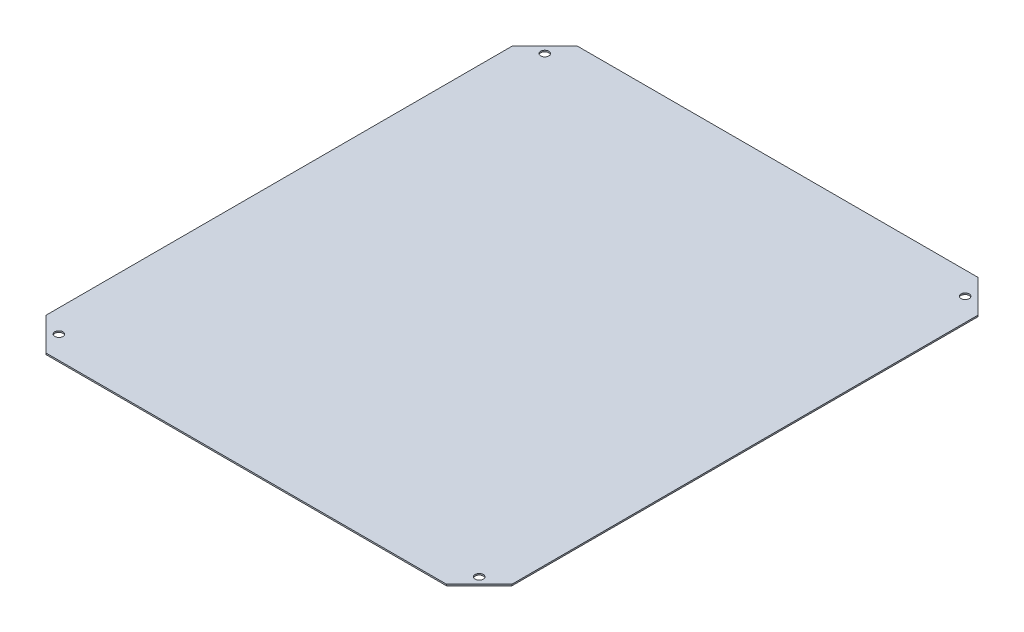
SolidWorks part; units mm, degrees
ref_plane "Front Plane" through (0, 0, 0) normal (0, 0, 1) x (1, 0, 0)
ref_plane "Top Plane" through (0, 0, 0) normal (0, 1, 0) x (1, 0, 0)
ref_plane "Right Plane" through (0, 0, 0) normal (1, 0, 0) x (0, 0, -1)
sketch "Sketch3" plane through (0, 0, 0) normal (0, 1, 0) x (1, 0, 0)
  line L4 (-57.0395, 93.017) -> (57.0395, 93.017)
  line L5 (57.0395, 93.017) -> (110.0725, 146.05)
  line L14 (110.0725, 146.05) -> (128.033, 128.0895)
  line L15 (128.033, 128.0895) -> (75, 75.0565)
  line L16 (75, 75.0565) -> (75, 0)
  line L17 (0, 0) -> (0, 93.017) construction
  line L18 (0, 0) -> (75, 0) construction
  line L19 (-75, 75.0565) -> (-75, -75.0565)
  line L20 (-128.033, 128.0895) -> (-75, 75.0565)
  line L21 (-110.0725, 146.05) -> (-128.033, 128.0895)
  line L22 (-57.0395, 93.017) -> (-110.0725, 146.05)
  line L23 (-57.0395, -93.017) -> (-110.0725, -146.05)
  line L24 (-110.0725, -146.05) -> (-128.033, -128.0895)
  line L25 (-128.033, -128.0895) -> (-75, -75.0565)
  line L26 (75, -75.0565) -> (75, 0)
  line L27 (128.033, -128.0895) -> (75, -75.0565)
  line L28 (110.0725, -146.05) -> (128.033, -128.0895)
  line L29 (57.0395, -93.017) -> (110.0725, -146.05)
  line L30 (-57.0395, -93.017) -> (57.0395, -93.017)
  point P5 (75, 37.5282)
  point P18 (-75, 0)
  dimension "D1" = 25.4
  dimension "D2" = 75
  dimension "D4" = 75
  dimension "D5" = 135
  dimension "D3" = 292.1
extrude "Sheet" add sketch "Sketch3" along normal blind 0.7937
fillet "Fillet1" radius 50 8 edges at (-75, 0.3969, 75.0565) (-57.0395, 0.3969, 93.017) (75, 0.3969, 75.0565) (57.0395, 0.3969, 93.017) (57.0395, 0.3969, -93.017) (75, 0.3969, -75.0565) (-75, 0.3969, -75.0565) (-57.0395, 0.3969, -93.017)
hole_wizard "M4 Clearance Hole1" positions "Sketch4" profile "Sketch5" hole size "M4" standard "ANSI Metric" end condition through all
sketch "Sketch4" plane through (0, 0.7937, 0) normal (0, 1, 0) x (1, 0, 0)
  line L0 (119.0528, 137.0697) -> (55.6644, 73.6814) construction
  line L1 (128.033, 128.0895) -> (110.0725, 146.05) construction
  line L2 (36.3288, 93.017) -> (75, 54.3458) construction
  point P0 (115.5172, 133.5342)
  point P15 (55.6644, 73.6814)
  dimension "D1" = 5
sketch "Sketch5" plane through (115.5172, 0.7937, -133.5342) normal (1, 0, 0) x (0, 0, 1)
  line L0 (0, 0) -> (0, 0.7937)
  line L1 (0, 0.7937) -> (2.25, 0.7937)
  line L2 (2.25, 0.7937) -> (2.25, 0)
  line L5 (2.25, 0) -> (0, 0)
  line L11 (0, -6.35) -> (0, 107.95) construction
  dimension "Thru Hole Dia." = 4.5
  dimension "Thru Hole Depth" = 0.7937
pattern_linear "HolePattern" [suppressed] count 6 spacing 10 of bodies 109
mirror "PatternMirror1" [suppressed] about plane through (0, 0, 0) normal (0, 0, 1)
mirror "PatternMirror2" [suppressed] about plane through (0, 0, 0) normal (1, 0, 0)
mirror "SingleHoleMirror1" about plane through (0, 0, 0) normal (0, 0, 1) of "M4 Clearance Hole1"
mirror "SingleHoleMirror2" about plane through (0, 0, 0) normal (1, 0, 0) of "SingleHoleMirror1"
sketch "Sketch6" plane through (0, 0.7937, 0) normal (0, 1, 0) x (1, 0, 0)
  line L0 (-128.033, 128.0895) -> (-128.033, -128.0895)
  line L2 (-89.6447, -89.7011) -> (-128.033, -128.0895) construction
  line L3 (-110.0725, -146.05) -> (110.0725, -146.05)
  line L4 (128.033, 128.0895) -> (128.033, -128.0895)
  line L5 (89.6447, 89.7011) -> (128.033, 128.0895) construction
  line L6 (75, -54.3458) -> (75, 54.3458) construction
  line L7 (128.033, -128.0895) -> (89.6447, -89.7011) construction
  line L8 (71.6841, -107.6617) -> (110.0725, -146.05) construction
  line L9 (-36.3288, -93.017) -> (36.3288, -93.017) construction
  line L10 (-110.0725, -146.05) -> (-71.6841, -107.6617) construction
  line L11 (-75, 54.3458) -> (-75, -54.3458) construction
  line L12 (-128.033, 128.0895) -> (-89.6447, 89.7011) construction
  line L13 (89.6447, 89.7011) -> (128.033, 128.0895)
  line L14 (75, -54.3458) -> (75, 54.3458)
  line L15 (128.033, -128.0895) -> (89.6447, -89.7011)
  line L16 (71.6841, -107.6617) -> (110.0725, -146.05)
  line L17 (-36.3288, -93.017) -> (36.3288, -93.017)
  line L18 (-110.0725, -146.05) -> (-71.6841, -107.6617)
  line L19 (-89.6447, -89.7011) -> (-128.033, -128.0895)
  line L20 (-75, 54.3458) -> (-75, -54.3458)
  line L21 (-128.033, 128.0895) -> (-89.6447, 89.7011)
  arc A0 (89.6447, 89.7011) -> (75, 54.3458) centre (125, 54.3458) ccw construction
  arc A1 (75, -54.3458) -> (89.6447, -89.7011) centre (125, -54.3458) ccw construction
  arc A2 (71.6841, -107.6617) -> (36.3288, -93.017) centre (36.3288, -143.017) ccw construction
  arc A3 (-36.3288, -93.017) -> (-71.6841, -107.6617) centre (-36.3288, -143.017) ccw construction
  arc A4 (-89.6447, -89.7011) -> (-75, -54.3458) centre (-125, -54.3458) ccw construction
  arc A5 (-75, 54.3458) -> (-89.6447, 89.7011) centre (-125, 54.3458) ccw construction
  arc A6 (89.6447, 89.7011) -> (75, 54.3458) centre (125, 54.3458) ccw
  arc A7 (75, -54.3458) -> (89.6447, -89.7011) centre (125, -54.3458) ccw
  arc A8 (71.6841, -107.6617) -> (36.3288, -93.017) centre (36.3288, -143.017) ccw
  arc A9 (-36.3288, -93.017) -> (-71.6841, -107.6617) centre (-36.3288, -143.017) ccw
  arc A10 (-89.6447, -89.7011) -> (-75, -54.3458) centre (-125, -54.3458) ccw
  arc A11 (-75, 54.3458) -> (-89.6447, 89.7011) centre (-125, 54.3458) ccw
extrude "FullSheetSideFlaps" add sketch "Sketch6" against normal up to surface (0.7937 mm away) up to face at (-115.5172, 0, 135.7842)
sketch "Sketch8" [suppressed] plane through (0, 0.7937, 0) normal (0, 1, 0) x (1, 0, 0)
  line L0 (-128.033, 128.0895) -> (-128.033, -128.0895)
  line L1 (-128.033, -128.0895) -> (-106.5774, -49.6627)
  line L2 (-103.033, -23.2749) -> (-103.033, 23.2749)
  line L3 (-106.5774, 49.6627) -> (-128.033, 128.0895)
  line L4 (0, -0.4366) -> (0, 0.4366) construction
  line L5 (106.5774, 49.6627) -> (128.033, 128.0895)
  line L6 (103.033, -23.2749) -> (103.033, 23.2749)
  line L7 (128.033, -128.0895) -> (106.5774, -49.6627)
  line L8 (128.033, 128.0895) -> (128.033, -128.0895)
  line L9 (-110.0725, -146.05) -> (110.0725, -146.05)
  line L10 (110.0725, -146.05) -> (39.1925, -121.05)
  line L11 (39.1925, -121.05) -> (-39.1925, -121.05)
  line L12 (-39.1925, -121.05) -> (-110.0725, -146.05)
  arc A0 (-103.033, 23.2749) -> (-106.5774, 49.6627) centre (-203.033, 23.2749) ccw
  arc A1 (-106.5774, -49.6627) -> (-103.033, -23.2749) centre (-203.033, -23.2749) ccw
  arc A2 (106.5774, -49.6627) -> (103.033, -23.2749) centre (203.033, -23.2749) cw
  arc A3 (103.033, 23.2749) -> (106.5774, 49.6627) centre (203.033, 23.2749) cw
  point P11 (-103.033, 0)
  point P27 (0, -121.05)
  dimension "D1" = 100
  dimension "D2" = 100
  dimension "D3" = 25
  dimension "D4" = 25
extrude "ReducedFlap" [suppressed] cut sketch "Sketch8" against normal up to next
sketch "Sketch9" plane through (0, 0.7937, 0) normal (0, 1, 0) x (1, 0, 0)
  line L0 (110.0725, 146.05) -> (71.6841, 107.6617) construction
  line L1 (36.3288, 93.017) -> (-36.3288, 93.017) construction
  line L2 (-71.6841, 107.6617) -> (-110.0725, 146.05) construction
  line L3 (110.0725, 146.05) -> (71.6841, 107.6617)
  line L4 (36.3288, 93.017) -> (-36.3288, 93.017)
  line L5 (-71.6841, 107.6617) -> (-110.0725, 146.05)
  line L6 (-110.0725, 146.05) -> (110.0725, 146.05)
  arc A0 (36.3288, 93.017) -> (71.6841, 107.6617) centre (36.3288, 143.017) ccw construction
  arc A1 (-71.6841, 107.6617) -> (-36.3288, 93.017) centre (-36.3288, 143.017) ccw construction
  arc A2 (36.3288, 93.017) -> (71.6841, 107.6617) centre (36.3288, 143.017) ccw
  arc A3 (-71.6841, 107.6617) -> (-36.3288, 93.017) centre (-36.3288, 143.017) ccw
extrude "CloseCannulusSide" add sketch "Sketch9" against normal up to surface (0.7937 mm away) up to face at (0, 0, -32.8604)
sketch "Sketch10" [suppressed] plane through (0, 0.7937, 0) normal (0, 1, 0) x (1, 0, 0)
  line L0 (128.033, 128.0895) -> (110.0725, 146.05) construction
  line L1 (110.0725, -146.05) -> (128.033, -128.0895) construction
  line L2 (128.033, -128.0895) -> (128.033, 128.0895) construction
  line L3 (-110.0725, -146.05) -> (110.0725, -146.05) construction
  line L4 (-128.033, -128.0895) -> (-110.0725, -146.05) construction
  line L5 (-128.033, 128.0895) -> (-128.033, -128.0895) construction
  line L6 (-110.0725, 146.05) -> (-128.033, 128.0895) construction
  line L7 (110.0725, 146.05) -> (-110.0725, 146.05) construction
  line L8 (128.033, 128.0895) -> (110.0725, 146.05)
  line L9 (110.0725, -146.05) -> (128.033, -128.0895)
  line L10 (128.033, -128.0895) -> (128.033, 128.0895)
  line L11 (-110.0725, -146.05) -> (110.0725, -146.05)
  line L12 (-128.033, -128.0895) -> (-110.0725, -146.05)
  line L13 (-128.033, 128.0895) -> (-128.033, -128.0895)
  line L14 (-110.0725, 146.05) -> (-128.033, 128.0895)
  line L15 (110.0725, 146.05) -> (-110.0725, 146.05)
  line L17 (-178.833, -196.85) -> (178.833, -196.85)
  line L18 (-178.833, -196.85) -> (-178.833, 196.85)
  line L19 (-178.833, 196.85) -> (178.833, 196.85)
  line L20 (178.833, -196.85) -> (178.833, 196.85)
  line L21 (-178.833, -196.85) -> (178.833, 196.85) construction
  line L22 (-178.833, 196.85) -> (178.833, -196.85) construction
  point P4 (0, 0)
  dimension "D1" = 50.8
  dimension "D2" = 50.8
extrude "ExcessAllSides" [suppressed] add sketch "Sketch10" against normal up to surface (0.7937 mm away) up to face at (0, 0, 0)
sketch "Sketch11" plane through (0, 0.7937, 0) normal (0, 1, 0) x (1, 0, 0)
  circle A0 centre (0, 0) radius 3.175
  circle A1 centre (19.05, 0) radius 3.175
  circle A2 centre (38.1, 0) radius 3.175
  circle A3 centre (57.15, 0) radius 3.175
  circle A4 centre (76.2, 0) radius 3.175
  circle A5 centre (19.05, 19.05) radius 3.175
  circle A6 centre (38.1, 19.05) radius 3.175
  circle A7 centre (57.15, 19.05) radius 3.175
  circle A8 centre (76.2, 19.05) radius 3.175
  circle A9 centre (19.05, 38.1) radius 3.175
  circle A10 centre (38.1, 38.1) radius 3.175
  circle A11 centre (57.15, 38.1) radius 3.175
  circle A12 centre (76.2, 38.1) radius 3.175
  circle A13 centre (19.05, 57.15) radius 3.175
  circle A14 centre (38.1, 57.15) radius 3.175
  circle A15 centre (57.15, 57.15) radius 3.175
  circle A16 centre (76.2, 57.15) radius 3.175
  circle A17 centre (19.05, 76.2) radius 3.175
  circle A18 centre (38.1, 76.2) radius 3.175
  circle A19 centre (57.15, 76.2) radius 3.175
  circle A20 centre (76.2, 76.2) radius 3.175
  circle A21 centre (0, 19.05) radius 3.175
  circle A22 centre (0, 38.1) radius 3.175
  circle A23 centre (0, 57.15) radius 3.175
  circle A24 centre (0, 76.2) radius 3.175
  dimension "D1" = 6.35
  dimension "D2" = 5
  dimension "D3" = 5
extrude "DrainageHoles" [suppressed] cut sketch "Sketch11" against normal up to next
mirror "Mirror1" [suppressed] about plane through (0, 0, 0) normal (0, 0, 1)
mirror "Mirror2" [suppressed] about plane through (0, 0, 0) normal (1, 0, 0)
equation "\"SheetLength\"= 258"
equation "\"D2@Sketch3\"=\"SheetWidth\" / 2 - \"SheetEdgeOffset\""
equation "\"SheetWidth\"=200"
equation "\"TabLength\"=75"
equation "\"D4@Sketch3\"= \"TabLength\""
equation "\"SheetEdgeOffset\"= 25mm"
equation "\"RawSheetSize\"=304.8"
equation "\"D3@Sketch3\"=\"RawSheetSize\" - \"SlopForLaserCutting\""
equation "\"SlopForLaserCutting\"= 0.5in"
equation "\"FlapDepth\"=25"
equation "\"D3@Sketch8\"=\"FlapDepth\""
equation "\"D4@Sketch8\"=\"FlapDepth\""
equation "\"D1@Sketch10\"=2in"
equation "\"D2@Sketch10\"=2in"
